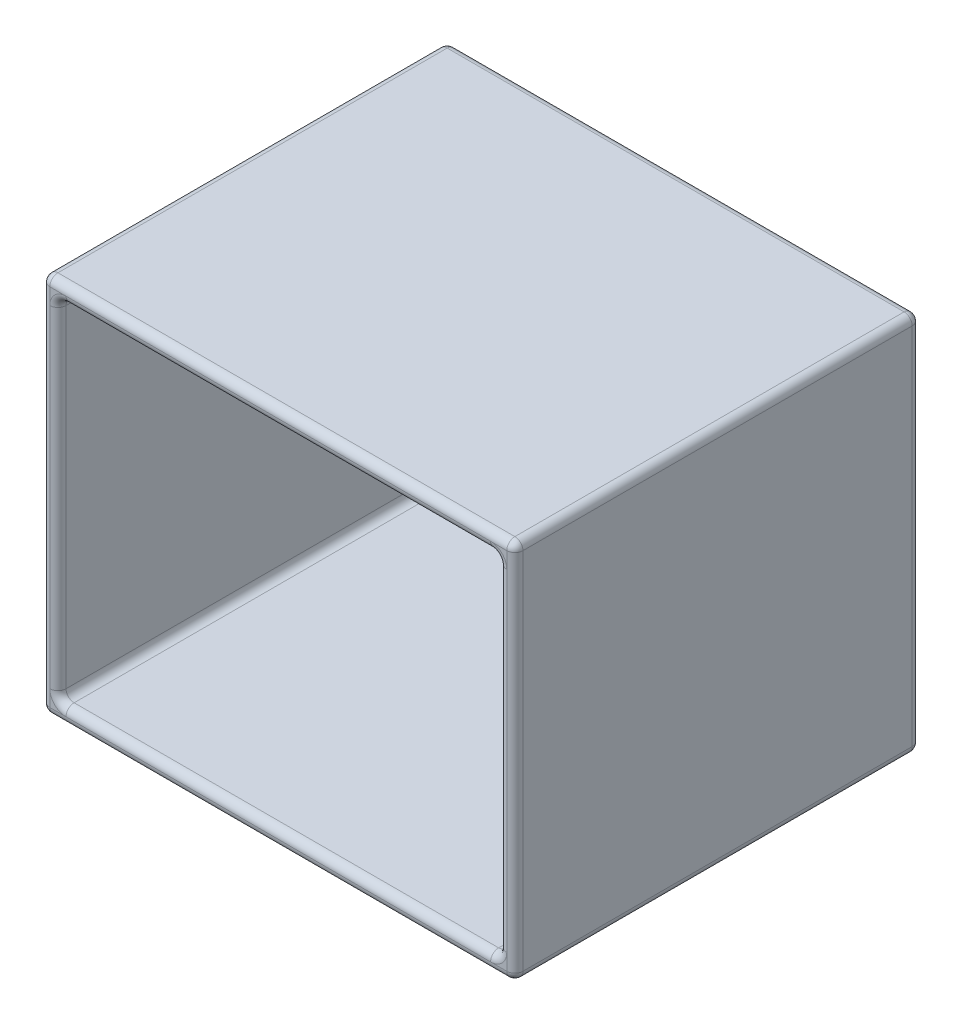
SolidWorks part; units mm, degrees
ref_plane "Alzado" through (0, 0, 0) normal (0, 0, 1) x (1, 0, 0)
ref_plane "Planta" through (0, 0, 0) normal (0, 1, 0) x (1, 0, 0)
ref_plane "Vista lateral" through (0, 0, 0) normal (1, 0, 0) x (0, 0, -1)
sketch "Croquis1" plane through (0, 0, 0) normal (0, 0, 1) x (1, 0, 0)
  line L0 (-135.89, 0) -> (135.89, 0) construction
  line L1 (0, -107.315) -> (0, 107.315) construction
  line L2 (-145.89, 117.315) -> (145.89, 117.315)
  line L3 (-135.89, 107.315) -> (135.89, 107.315)
  line L4 (-135.89, 107.315) -> (-135.89, -107.315)
  line L5 (-135.89, -107.315) -> (135.89, -107.315)
  line L6 (135.89, 107.315) -> (135.89, -107.315)
  line L7 (145.89, 117.315) -> (145.89, -117.315)
  line L8 (-145.89, -117.315) -> (145.89, -117.315)
  line L9 (-145.89, 117.315) -> (-145.89, -117.315)
  point P4 (0, 0)
  point P8 (0, 0)
  dimension "D1" = 271.78
  dimension "D2" = 214.63
  dimension "D3" = 10
extrude "Saliente-Extruir1" add sketch "Croquis1" along normal blind 250
sketch "Croquis2" plane through (0, 0, 0) normal (0, 0, 1) x (1, 0, 0)
  line L0 (145.89, -117.315) -> (145.89, 117.315) construction
  line L1 (145.89, 117.315) -> (-145.89, 117.315) construction
  line L2 (-145.89, 117.315) -> (-145.89, -117.315) construction
  line L3 (-145.89, -117.315) -> (145.89, -117.315) construction
  line L4 (145.89, -117.315) -> (145.89, 117.315)
  line L5 (145.89, 117.315) -> (-145.89, 117.315)
  line L6 (-145.89, 117.315) -> (-145.89, -117.315)
  line L7 (-145.89, -117.315) -> (145.89, -117.315)
extrude "Saliente-Extruir2" add sketch "Croquis2" along normal blind 10
fillet "Redondeo1" radius 5 24 edges at (0, -107.315, 250) (-135.89, -107.315, 130) (-135.89, 0, 250) (0, -107.315, 10) (-135.89, 0, 10) (135.89, 0, 250) (135.89, -107.315, 130) (135.89, 0, 10) (0, -117.315, 250) (145.89, 0, 250) (145.89, -117.315, 125) (-145.89, 0, 250) (-145.89, -117.315, 125) (0, 117.315, 250) (-145.89, 117.315, 125) (145.89, 117.315, 125) (-135.89, 107.315, 130) (0, 107.315, 250) (135.89, 107.315, 130) (0, 107.315, 10) (0, -117.315, 0) (145.89, 0, 0) (0, 117.315, 0) (-145.89, 0, 0)
